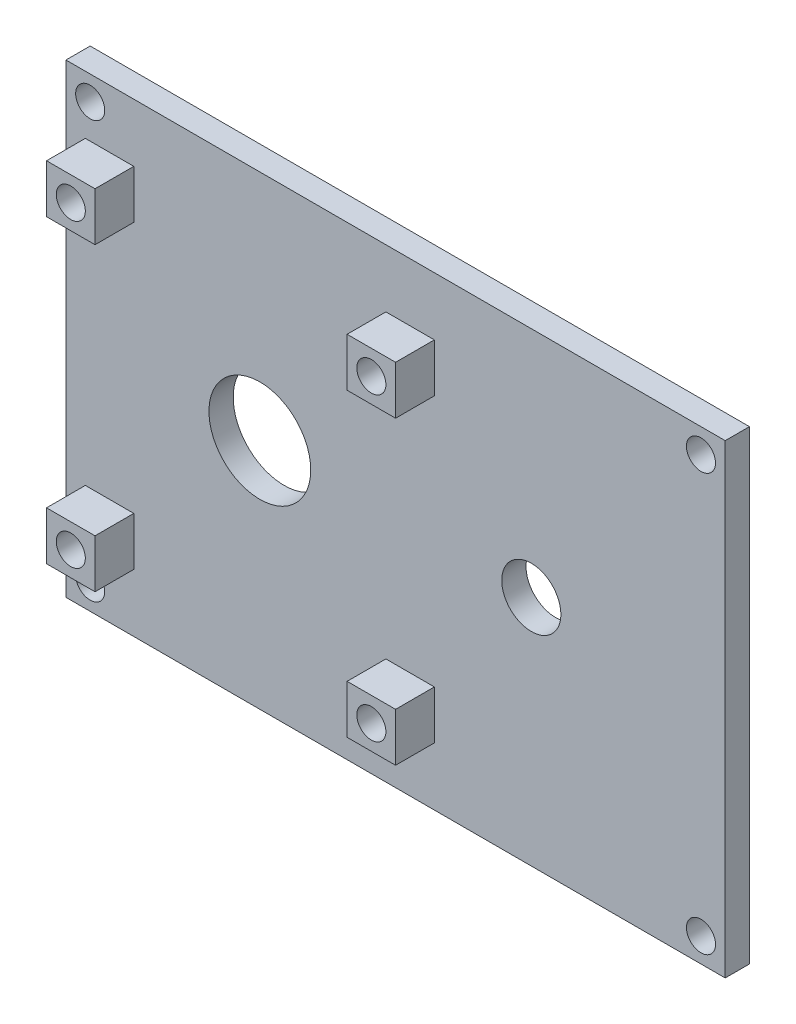
SolidWorks part; units mm, degrees
ref_plane "Přední rovina" through (0, 0, 0) normal (0, 0, 1) x (1, 0, 0)
ref_plane "Horní rovina" through (0, 0, 0) normal (0, 1, 0) x (1, 0, 0)
ref_plane "Pravá rovina" through (0, 0, 0) normal (1, 0, 0) x (0, 0, -1)
sketch "Skica1" plane through (0, 0, 0) normal (0, 0, 1) x (1, 0, 0)
  line L1 (-34, -24) -> (34, -24)
  line L2 (-34, -24) -> (-34, 24)
  line L3 (-34, 24) -> (34, 24)
  line L4 (34, -24) -> (34, 24)
  line L5 (-34, -24) -> (34, 24) construction
  line L6 (-34, 24) -> (34, -24) construction
  line L7 (-34, 24) -> (-23.5, 24)
  line L8 (-34, 24) -> (-34, 9)
  circle A0 centre (-31.5, 21.5) radius 1.5
  circle A1 centre (31.5, 21.5) radius 1.5
  circle A2 centre (31.5, -21.5) radius 1.5
  circle A3 centre (-31.5, -21.5) radius 1.5
  circle A4 centre (-14, 0) radius 5.25
  circle A5 centre (14, 0) radius 3.05
  point P0 (0, 0)
  point P20 (-34, 0)
  dimension "D5" = 3
  dimension "D6" = 3
  dimension "D9" = 3
  dimension "D12" = 3
  dimension "D15" = 10.5
  dimension "D17" = 6.1
  dimension "D1" = 48
  dimension "D2" = 68
  dimension "D3" = 2.5
  dimension "D4" = 2.5
  dimension "D7" = 2.5
  dimension "D8" = 2.5
  dimension "D10" = 2.5
  dimension "D11" = 2.5
  dimension "D13" = 2.5
  dimension "D14" = 2.5
  dimension "D16" = 20
  dimension "D18" = 28
extrude "Přidat vysunutím1" add sketch "Skica1" along normal blind 2.5 contours L1 L4 L3 L2 A3 A2 A1 A0 region at (0.2574, 0, 0)
sketch "Skica2" plane through (0, 0, 2.5) normal (0, 0, 1) x (1, 0, 0)
  line L0 (-29.5, -15.5) -> (1.5, 15.5) construction
  line L1 (-29.5, 15.5) -> (1.5, -15.5) construction
  line L3 (-32, 18) -> (-27, 18)
  line L4 (-32, 18) -> (-32, 13)
  line L5 (-32, 13) -> (-27, 13)
  line L6 (-27, 18) -> (-27, 13)
  line L7 (-32, 18) -> (-27, 13) construction
  line L8 (-32, 13) -> (-27, 18) construction
  line L9 (-1, 18) -> (4, 18)
  line L10 (-1, 18) -> (-1, 13)
  line L11 (-1, 13) -> (4, 13)
  line L12 (4, 18) -> (4, 13)
  line L13 (-1, 18) -> (4, 13) construction
  line L14 (-1, 13) -> (4, 18) construction
  line L15 (-1, -13) -> (4, -13)
  line L16 (-1, -13) -> (-1, -18)
  line L17 (-1, -18) -> (4, -18)
  line L18 (4, -13) -> (4, -18)
  line L19 (-1, -13) -> (4, -18) construction
  line L20 (-1, -18) -> (4, -13) construction
  line L21 (-32, -13) -> (-27, -13)
  line L22 (-32, -13) -> (-32, -18)
  line L23 (-32, -18) -> (-27, -18)
  line L24 (-27, -13) -> (-27, -18)
  line L25 (-32, -13) -> (-27, -18) construction
  line L26 (-32, -18) -> (-27, -13) construction
  circle A0 centre (-29.5, 15.5) radius 1.5
  circle A1 centre (1.5, 15.5) radius 1.5
  circle A2 centre (1.5, -15.5) radius 1.5
  circle A3 centre (-29.5, -15.5) radius 1.5
  circle A5 centre (-14, 0) radius 5.25 construction
  circle A6 centre (-14, 0) radius 5.25 construction
  point P14 (-14, 0)
  dimension "D1" = 3
  dimension "D2" = 31
  dimension "D3" = 31
  dimension "D4" = 5
  dimension "D5" = 5
  dimension "D6" = 5
  dimension "D7" = 5
  dimension "D8" = 5
  dimension "D9" = 5
  dimension "D10" = 5
extrude "Přidat vysunutím2" add sketch "Skica2" along normal blind 4
sketch "Skica5" plane through (0, 0, 2.5) normal (0, 0, 1) x (1, 0, 0)
  circle A0 centre (-29.5, 15.5) radius 1.5
  circle A1 centre (-29.5, 15.5) radius 1.5 construction
  circle A2 centre (1.5, 15.5) radius 1.5
  circle A3 centre (1.5, 15.5) radius 1.5 construction
  circle A4 centre (1.5, -15.5) radius 1.5
  circle A5 centre (1.5, -15.5) radius 1.5 construction
  circle A6 centre (-29.5, -15.5) radius 1.5
  circle A7 centre (-29.5, -15.5) radius 1.5 construction
extrude "Odebrat vysunutím1" cut sketch "Skica5" against normal blind 2.5
chamfer "Zkosení1" distance 1.5 angle 45 4 edges at (3, -15.5, 0) (-28, -15.5, 0) (-28, 15.5, 0) (3, 15.5, 0)
